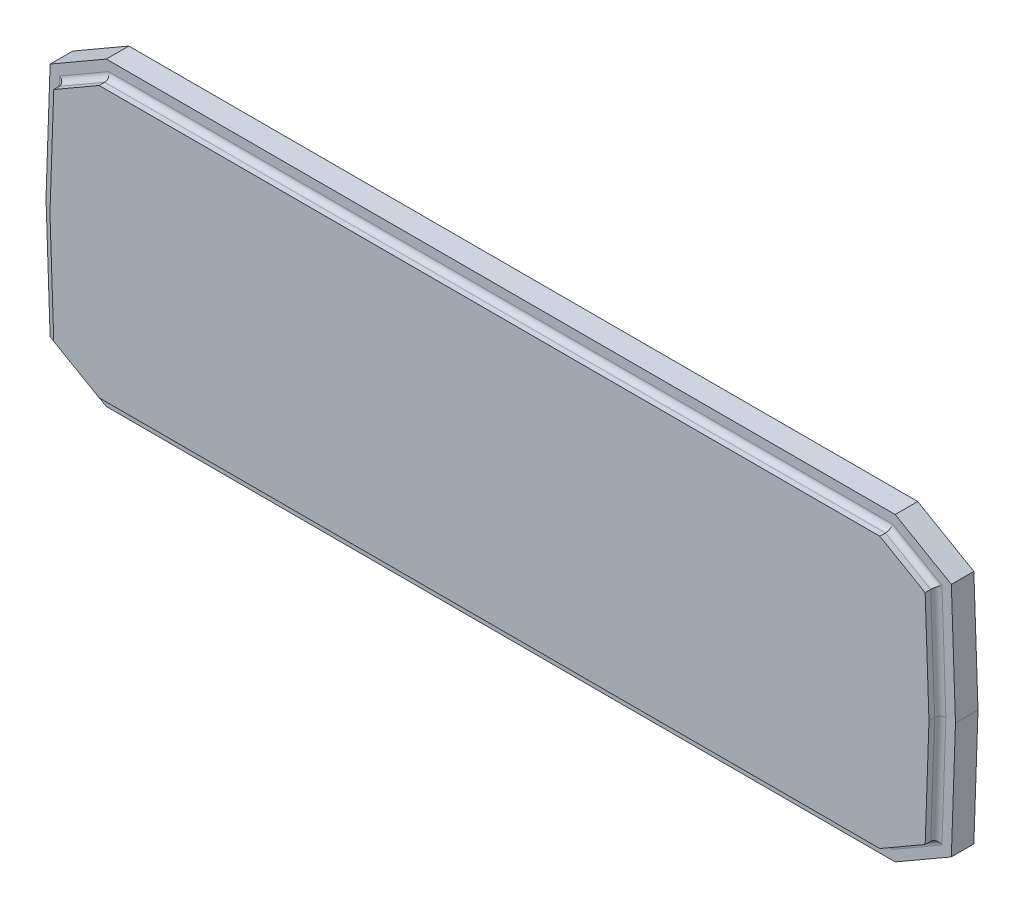
SolidWorks part; units mm, degrees
material "ABS"
ref_plane "Płaszczyzna przednia" through (0, 0, 0) normal (0, 0, 1) x (1, 0, 0)
ref_plane "Płaszczyzna górna" through (0, 0, 0) normal (0, 1, 0) x (1, 0, 0)
ref_plane "Płaszczyzna prawa" through (0, 0, 0) normal (1, 0, 0) x (0, 0, -1)
ref_plane "Plane1" through (0, 0, 2) normal (0, 0, 1) x (1, 0, 0)
sketch "Sketch1" plane through (0, 0, 2) normal (0, 0, 1) x (1, 0, 0)
  line L0 (-14.3407, 2.3713) -> (-14.7064, -8.101)
  line L1 (-14.7064, -8.101) -> (-14.3407, -18.5733)
  line L2 (-14.3407, -18.5733) -> (-9.3564, -21.451)
  line L3 (-9.3564, -21.451) -> (60.6436, -21.451)
  line L4 (60.6436, -21.451) -> (65.6279, -18.5733)
  line L5 (65.6279, -18.5733) -> (65.9936, -8.101)
  line L6 (65.9936, -8.101) -> (65.6279, 2.3713)
  line L7 (65.6279, 2.3713) -> (60.6436, 5.249)
  line L8 (60.6436, 5.249) -> (-9.3564, 5.249)
  line L9 (-9.3564, 5.249) -> (-14.3407, 2.3713)
extrude "Boss-Extrude1" add sketch "Sketch1" against normal blind 2
sketch "Sketch2" plane through (0, 0, 2) normal (0, 0, 1) x (1, 0, 0)
  line L0 (-13.3556, -8.101) -> (-13.0176, 1.5763)
  line L1 (-13.0176, 1.5763) -> (-8.9947, 3.899)
  line L2 (-8.9947, 3.899) -> (60.2819, 3.899)
  line L3 (60.2819, 3.899) -> (64.3048, 1.5763)
  line L4 (64.3048, 1.5763) -> (64.6428, -8.101)
  line L5 (64.6428, -8.101) -> (64.3048, -17.7784)
  line L6 (64.3048, -17.7784) -> (60.2819, -20.101)
  line L7 (60.2819, -20.101) -> (-8.9947, -20.101)
  line L8 (-8.9947, -20.101) -> (-13.0176, -17.7784)
  line L9 (-13.0176, -17.7784) -> (-13.3556, -8.101)
extrude "Boss-Extrude2" add sketch "Sketch2" along normal blind 1
sketch "Sketch3" plane through (0, 0, 0) normal (0, 0, -1) x (-1, 0, 0)
  line L0 (-64.9419, 1.9591) -> (-65.2932, -8.101)
  line L1 (-65.2932, -8.101) -> (-64.9419, -18.1611)
  line L2 (-64.9419, -18.1611) -> (-60.456, -20.751)
  line L3 (-60.456, -20.751) -> (9.1688, -20.751)
  line L4 (9.1688, -20.751) -> (13.6547, -18.1611)
  line L5 (13.6547, -18.1611) -> (14.006, -8.101)
  line L6 (14.006, -8.101) -> (13.6547, 1.9591)
  line L7 (13.6547, 1.9591) -> (9.1688, 4.549)
  line L8 (9.1688, 4.549) -> (-60.456, 4.549)
  line L9 (-60.456, 4.549) -> (-64.9419, 1.9591)
extrude "Cut-Extrude1" cut sketch "Sketch3" against normal blind 1.45
sketch "Sketch4" plane through (0, 0, 1.45) normal (0, 0, -1) x (-1, 0, 0)
  line L0 (-63.4921, -8.101) -> (-63.1778, 0.8991)
  line L1 (-63.1778, 0.8991) -> (-59.9737, 2.749)
  line L2 (-59.9737, 2.749) -> (8.6865, 2.749)
  line L3 (8.6865, 2.749) -> (11.8906, 0.8991)
  line L4 (11.8906, 0.8991) -> (12.2049, -8.101)
  line L5 (12.2049, -8.101) -> (11.8906, -17.1012)
  line L6 (11.8906, -17.1012) -> (8.6865, -18.951)
  line L7 (8.6865, -18.951) -> (-59.9737, -18.951)
  line L8 (-59.9737, -18.951) -> (-63.1778, -17.1012)
  line L9 (-63.1778, -17.1012) -> (-63.4921, -8.101)
extrude "Boss-Extrude3" add sketch "Sketch4" along normal blind 1.45
fillet "Fillet1" radius 0.5 10 edges at (-11.0061, -18.9397, 2) (-13.1866, -12.9397, 2) (-13.1866, -3.2624, 2) (25.6436, -20.101, 2) (-11.0061, 2.7376, 2) (62.2934, -18.9397, 2) (25.6436, 3.899, 2) (64.4738, -3.2624, 2) (64.4738, -12.9397, 2) (62.2934, 2.7376, 2) tangent propagation no
fillet "Fillet2" radius 0.5 10 edges at (-13.8303, -13.1311, 1.45) (-13.8303, -3.071, 1.45) (-11.4117, -19.4561, 1.45) (-11.4117, 3.254, 1.45) (25.6436, -20.751, 1.45) (25.6436, 4.549, 1.45) (62.699, -19.4561, 1.45) (62.699, 3.254, 1.45) (65.1175, -13.1311, 1.45) (65.1175, -3.071, 1.45) tangent propagation no
fillet "Fillet3" radius 0.5 10 edges at (-10.2886, 1.824, 1.45) (-12.0477, -12.6011, 1.45) (-12.0477, -3.601, 1.45) (25.6436, 2.749, 1.45) (-10.2886, -18.0261, 1.45) (61.5758, 1.824, 1.45) (25.6436, -18.951, 1.45) (63.3349, -12.6011, 1.45) (63.3349, -3.601, 1.45) (61.5758, -18.0261, 1.45) tangent propagation no
